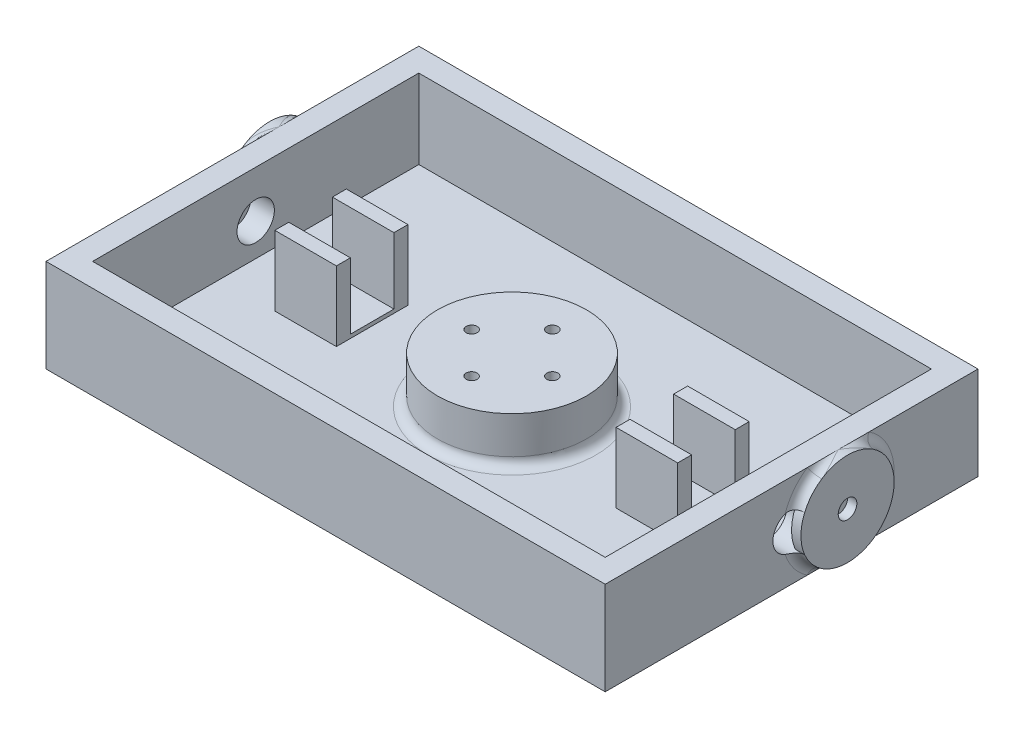
SolidWorks part; units mm, degrees
ref_plane "Front Plane" through (0, 0, 0) normal (0, 0, 1) x (1, 0, 0)
ref_plane "Top Plane" through (0, 0, 0) normal (0, 1, 0) x (1, 0, 0)
ref_plane "Right Plane" through (0, 0, 0) normal (1, 0, 0) x (0, 0, -1)
sketch "Sketch4" plane through (0, 0, 0) normal (0, 1, 0) x (1, 0, 0)
  line L1 (0, 0) -> (152.4, 0)
  line L2 (0, 0) -> (0, 101.6)
  line L3 (0, 101.6) -> (152.4, 101.6)
  line L4 (152.4, 0) -> (152.4, 101.6)
  dimension "D1" = 152.4
  dimension "D2" = 101.6
extrude "Boss-Extrude2" add sketch "Sketch4" along normal blind 3.81
sketch "Sketch6" plane through (0, 3.81, 0) normal (0, 1, 0) x (1, 0, 0)
  line L0 (0, 101.6) -> (0, 0) construction
  line L1 (12.7, 32.131) -> (39.37, 32.131)
  line L2 (0, 57.531) -> (0, 44.069)
  line L3 (12.7, 44.069) -> (39.37, 44.069)
  line L4 (39.37, 32.131) -> (39.37, 44.069)
  line L5 (152.4, 101.6) -> (0, 101.6) construction
  line L6 (6.35, 71.501) -> (6.35, 95.25)
  line L7 (6.35, 71.501) -> (12.7, 71.501)
  line L8 (0, 71.501) -> (0, 55.499)
  line L9 (6.35, 55.499) -> (12.7, 55.499)
  line L10 (12.7, 71.501) -> (12.7, 44.069)
  line L11 (6.35, 6.35) -> (146.05, 6.35)
  line L12 (6.35, 6.35) -> (6.35, 55.499)
  line L13 (6.35, 95.25) -> (146.05, 95.25)
  line L14 (146.05, 6.35) -> (146.05, 95.25)
  line L15 (12.7, 32.131) -> (12.7, 55.499)
  line L16 (152.4, 0) -> (152.4, 101.6) construction
  line L17 (0, 0) -> (152.4, 0) construction
  line L18 (6.35, 71.501) -> (6.35, 55.499)
  point P6 (39.37, 38.1)
  line M4 (0, 101.6) -> (0, 0)
  line M5 (0, 0) -> (152.4, 0)
  line M6 (152.4, 0) -> (152.4, 101.6)
  line M7 (152.4, 101.6) -> (0, 101.6)
  dimension "D1" = 63.5
  dimension "D2" = 39.37
  dimension "D3" = 11.938
  dimension "D4" = 12.7
  dimension "D5" = 16.002
  dimension "D6" = 6.35
  dimension "D7" = 6.35
  dimension "D8" = 6.35
  dimension "D9" = 6.35
extrude "Boss-Extrude3" add sketch "Sketch6" along normal blind 21.59 contours L18 L6 L13 L14 L11 L12 M7 M4 M5 M6 region at (1.8316, 3.81, -64.516)
sketch "Sketch7" plane through (0, 0, 0) normal (-1, 0, 0) x (0, 0, 1)
  line L0 (-101.6, 25.4) -> (-101.6, 0) construction
  line L2 (-101.6, 25.4) -> (0, 25.4) construction
  circle A0 centre (-50.8, 12.7) radius 5.0894
  point P4 (-101.6, 12.7)
  dimension "D1" = 50.8
  dimension "D2" = 12.7
extrude "Cut-Extrude1" cut sketch "Sketch7" against normal through all
sketch "Sketch8" plane through (0, 3.81, 0) normal (0, 1, 0) x (1, 0, 0)
  line L1 (38.0905, 44.8593) -> (21.3055, 44.8593)
  line L2 (38.0905, 44.8593) -> (38.0905, 56.7407)
  line L3 (38.0905, 56.7407) -> (21.3055, 56.7407)
  line L4 (21.3055, 44.8593) -> (21.3055, 56.7407)
  line L6 (76.2, 6.35) -> (76.2, 95.25) construction
  line L7 (21.3055, 56.7407) -> (38.0905, 56.7407)
  line L8 (21.3055, 56.7407) -> (21.3055, 60.5507)
  line L9 (21.3055, 60.5507) -> (38.0905, 60.5507)
  line L10 (38.0905, 56.7407) -> (38.0905, 60.5507)
  line L11 (21.3055, 44.8593) -> (38.0905, 44.8593)
  line L12 (21.3055, 44.8593) -> (21.3055, 41.0493)
  line L13 (21.3055, 41.0493) -> (38.0905, 41.0493)
  line L14 (38.0905, 44.8593) -> (38.0905, 41.0493)
  line L15 (6.35, 6.35) -> (146.05, 6.35) construction
  line L16 (6.35, 95.25) -> (146.05, 95.25) construction
  line L17 (114.3095, 56.7407) -> (131.0945, 56.7407)
  line L18 (131.0945, 44.8593) -> (131.0945, 56.7407)
  line L19 (114.3095, 44.8593) -> (131.0945, 44.8593)
  line L20 (114.3095, 44.8593) -> (114.3095, 56.7407)
  line L21 (0, 0) -> (152.4, 0) construction
  point P22 (21.3055, 50.8)
  dimension "D3" = 3.81
  dimension "D4" = 3.81
  dimension "D5" = 50.8
extrude "Boss-Extrude4" add sketch "Sketch8" along normal blind 1.016 contours L4 L1 L2 L3 | L20 L19 L18 L17 region at (29.698, 3.81, -50.8) region at (122.702, 3.81, -50.8)
sketch "Sketch9" plane through (0, 3.81, 0) normal (0, 1, 0) x (1, 0, 0)
  line L5 (131.0945, 44.8593) -> (115.8545, 44.8593)
  line L9 (38.0905, 44.8593) -> (21.3055, 44.8593)
  line L10 (38.0905, 44.8593) -> (38.0905, 41.0493)
  line L11 (38.0905, 41.0493) -> (21.3055, 41.0493)
  line L12 (21.3055, 44.8593) -> (21.3055, 41.0493)
  line L13 (38.0905, 56.7407) -> (21.3055, 56.7407)
  line L14 (38.0905, 56.7407) -> (38.0905, 60.5507)
  line L15 (38.0905, 60.5507) -> (21.3055, 60.5507)
  line L16 (21.3055, 56.7407) -> (21.3055, 60.5507)
  line L18 (131.0945, 44.8593) -> (114.3095, 44.8593)
  line L19 (131.0945, 44.8593) -> (131.0945, 41.0493)
  line L20 (131.0945, 41.0493) -> (114.3095, 41.0493)
  line L21 (114.3095, 44.8593) -> (114.3095, 41.0493)
  line L22 (131.0945, 56.7407) -> (114.3095, 56.7407)
  line L23 (131.0945, 56.7407) -> (131.0945, 60.5507)
  line L24 (131.0945, 60.5507) -> (114.3095, 60.5507)
  line L25 (114.3095, 56.7407) -> (114.3095, 60.5507)
  dimension "D1" = 3.81
  dimension "D2" = 3.81
  dimension "D3" = 3.81
  dimension "D4" = 3.81
sketch "Sketch11" plane through (0, 0, 0) normal (-1, 0, 0) x (0, 0, 1)
  circle A0 centre (-63.5, 12.7) radius 12.7
extrude "Boss-Extrude6" add sketch "Sketch11" along normal blind 2.54
fillet "Fillet1" radius 2.54 1 edges at (0, 12.7, -76.2)
sketch "Sketch12" plane through (-2.54, 0, 0) normal (-1, 0, 0) x (0, 0, 1)
  circle A0 centre (-63.5, 12.7) radius 2.54
  dimension "D1" = 5.08
extrude "Cut-Extrude2" cut sketch "Sketch12" against normal blind 2.54
sketch "Sketch13" plane through (152.4, 0, 0) normal (1, 0, 0) x (0, 0, -1)
  circle A0 centre (63.5, 12.7) radius 12.7
extrude "Boss-Extrude7" add sketch "Sketch13" along normal blind 2.54
fillet "Fillet2" radius 2.54 1 edges at (152.4, 12.7, -76.2)
sketch "Sketch14" plane through (154.94, 0, 0) normal (1, 0, 0) x (0, 0, -1)
  circle A0 centre (63.5, 12.7) radius 2.54
  dimension "D1" = 5.08
extrude "Cut-Extrude3" cut sketch "Sketch14" against normal blind 2.54
sketch "Sketch15" plane through (0, 3.81, 0) normal (0, 1, 0) x (1, 0, 0)
  line L0 (76.2, 6.35) -> (76.2, 95.25) construction
  line L1 (6.35, 6.35) -> (146.05, 6.35) construction
  line L2 (6.35, 95.25) -> (146.05, 95.25) construction
  line L3 (146.05, 50.8) -> (76.2, 50.8) construction
  line L4 (146.05, 6.35) -> (146.05, 95.25) construction
  circle A0 centre (76.2, 50.8) radius 20.32
  dimension "D1" = 40.64
extrude "Boss-Extrude8" add sketch "Sketch9" along normal blind 19.05 contours L24 L25 L22 L23 | L19 L20 L21 L18 | L15 L16 L13 L14 | L9 L12 L11 L10
extrude "Boss-Extrude9" add sketch "Sketch15" along normal blind 12.7
fillet "Fillet3" radius 2.54 1 edges at (76.2, 3.81, -71.12)
sketch "Sketch16" plane through (0, 16.51, 0) normal (0, 1, 0) x (1, 0, 0)
  circle A0 centre (76.2, 50.8) radius 11
  circle A1 centre (65.2, 50.8) radius 1.5
  circle A2 centre (76.2, 61.8) radius 1.5
  circle A3 centre (87.2, 50.8) radius 1.5
  circle A4 centre (76.2, 39.8) radius 1.5
  dimension "D1" = 22
  dimension "D2" = 3
  dimension "D3" = 3
  dimension "D4" = 3
  dimension "D5" = 3
extrude "Cut-Extrude4" cut sketch "Sketch16" against normal blind 7.62 contours A0 A3 | A0 A3 | A0 A2 | A0 A2 | A1 | A4 region at (86.5453, 16.51, -50.8) region at (87.8178, 16.51, -50.8) region at (76.2, 16.51, -61.1453) region at (76.2, 16.51, -62.4178)
